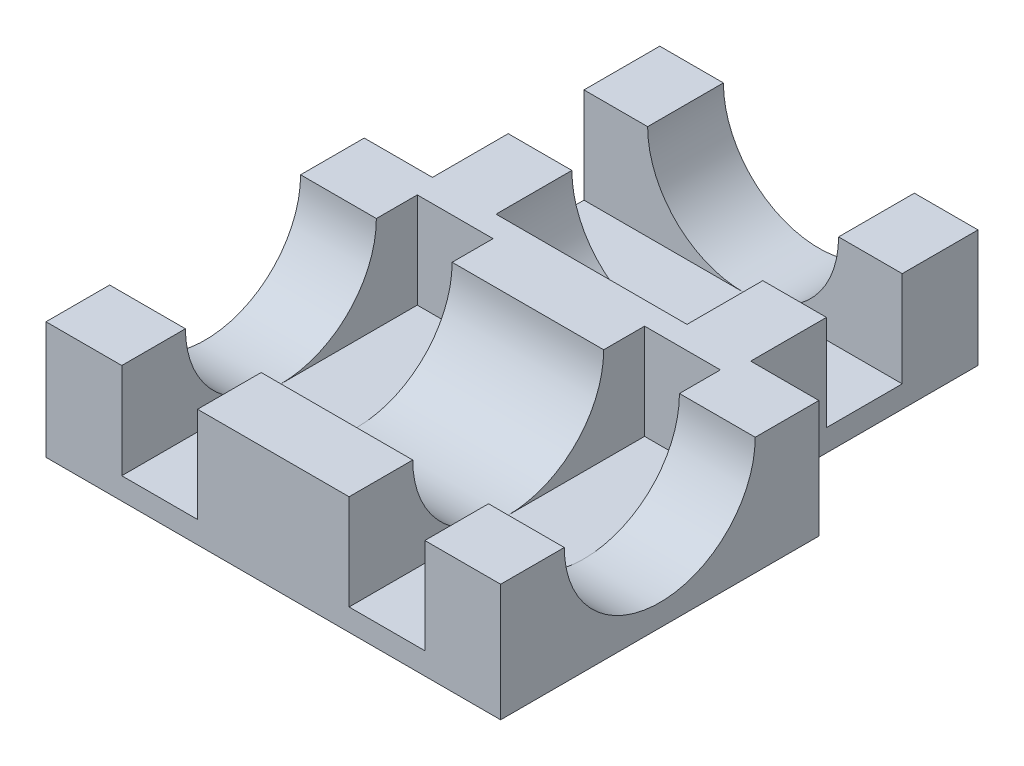
SolidWorks part; units mm, degrees
material "3.1355 (EN-AW 2024)"
ref_plane "Front" through (0, 0, 0) normal (0, 0, 1) x (1, 0, 0)
ref_plane "Top" through (0, 0, 0) normal (0, 1, 0) x (1, 0, 0)
ref_plane "Right" through (0, 0, 0) normal (1, 0, 0) x (0, 0, -1)
sketch "Эскиз1" plane through (0, 0, 0) normal (0, 1, 0) x (1, 0, 0)
  line L0 (0, 0) -> (0, 8.4)
  line L1 (0, 8.4) -> (0, 33.6)
  line L2 (0, 33.6) -> (0, 42)
  line L3 (60, 0) -> (0, 0)
  line L4 (0, 42) -> (9, 42)
  line L5 (10, 42) -> (20, 42) construction
  line L6 (20, 42) -> (30, 42) construction
  line L7 (60, 0) -> (60, 42)
  line L8 (60, 42) -> (51, 42)
  line L9 (30, 42) -> (30, 72) construction
  line L10 (51, 72) -> (9, 72)
  line L11 (9, 72) -> (9, 42)
  line L12 (51, 72) -> (51, 42)
  line L13 (9, 42) -> (10, 42) construction
  line L14 (51, 42) -> (30, 42) construction
  point P15 (10, 38.702)
  point P16 (52.6874, 36.7109)
  dimension "D1" = 25.2
  dimension "D2" = 8.4
  dimension "D3" = 8.4
  dimension "D4" = 10
  dimension "D5" = 10
  dimension "D6" = 10
  dimension "D7" = 60
  dimension "D8" = 30
  dimension "D9" = 21
extrude "Бобышка-Вытянуть1" add sketch "Эскиз1" along normal blind 15.5 contours L12 L10 L11 L4 L2 L1 L0 L3 L7 L8 region at (30, 0, -33)
sketch "Эскиз2" plane through (0, 0, 0) normal (-1, 0, 0) x (0, 0, 1)
  line L0 (-21, 15.5) -> (-21, 0) construction
  line L1 (0, 15.5) -> (-42, 15.5) construction
  line L2 (0, 0) -> (-42, 0) construction
  line L4 (-33.6, 15.5) -> (-8.4, 15.5)
  arc A0 (-33.6, 15.5) -> (-8.4, 15.5) centre (-21, 15.5) ccw
  dimension "D2" = 12.6
extrude "Вырез-Вытянуть1" cut sketch "Эскиз2" against normal through all
sketch "Эскиз3" plane through (0, 0, -72) normal (0, 0, -1) x (-1, 0, 0)
  line L0 (-30, 15.5) -> (-30, 0) construction
  line L1 (-51, 15.5) -> (-9, 15.5) construction
  line L2 (-51, 0) -> (-9, 0) construction
  line L3 (-42.6, 15.5) -> (-17.4, 15.5)
  arc A0 (-42.6, 15.5) -> (-17.4, 15.5) centre (-30, 15.5) ccw
  dimension "D1" = 12.6
extrude "Вырез-Вытянуть2" cut sketch "Эскиз3" against normal blind 30
sketch "Эскиз4" plane through (51, 0, 0) normal (1, 0, 0) x (0, 0, -1)
  line L0 (57, 15.5) -> (57, 0) construction
  line L1 (72, 15.5) -> (42, 15.5) construction
  line L2 (72, 0) -> (42, 0) construction
  line L3 (52, 2.9) -> (62, 2.9)
  line L4 (62, 15.5) -> (52, 15.5)
  line L5 (52, 15.5) -> (52, 2.9)
  line L6 (62, 15.5) -> (62, 2.9)
  point P10 (57, 2.9)
  dimension "D1" = 5
  dimension "D2" = 12.6
extrude "Вырез-Вытянуть3" cut sketch "Эскиз4" against normal through all
sketch "Эскиз5" plane through (0, 0, 0) normal (0, 0, 1) x (1, 0, 0)
  line L0 (30, 15.5) -> (30, 0) construction
  line L1 (60, 15.5) -> (0, 15.5) construction
  line L2 (60, 0) -> (0, 0) construction
  line L3 (10, 2.9) -> (20, 2.9)
  line L4 (10, 15.5) -> (10, 2.9)
  line L5 (10, 15.5) -> (20, 15.5)
  line L6 (0, 15.5) -> (0, 0) construction
  line L7 (20, 15.5) -> (20, 2.9)
  line L8 (40, 15.5) -> (40, 2.9)
  line L9 (50, 15.5) -> (40, 15.5)
  line L10 (50, 15.5) -> (50, 2.9)
  line L11 (50, 2.9) -> (40, 2.9)
  dimension "D1" = 10
  dimension "D2" = 12.6
  dimension "D3" = 10
extrude "Вырез-Вытянуть4" cut sketch "Эскиз5" against normal blind 39
